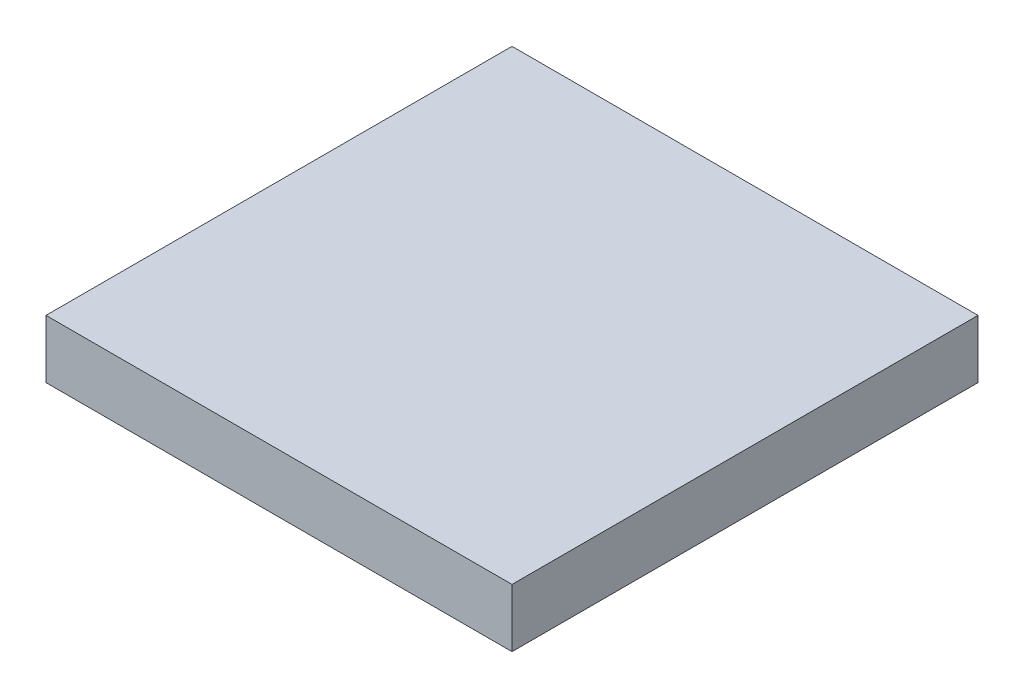
SolidWorks part; units mm, degrees
ref_plane "Plan de face" through (0, 0, 0) normal (0, 0, 1) x (1, 0, 0)
ref_plane "Plan de dessus" through (0, 0, 0) normal (0, 1, 0) x (1, 0, 0)
ref_plane "Plan de droite" through (0, 0, 0) normal (1, 0, 0) x (0, 0, -1)
sketch "Esquisse1" plane through (0, 0, 0) normal (0, 1, 0) x (1, 0, 0)
  line L1 (-120, -120) -> (120, -120)
  line L2 (-120, -120) -> (-120, 120)
  line L3 (-120, 120) -> (120, 120)
  line L4 (120, -120) -> (120, 120)
  line L5 (-120, -120) -> (120, 120) construction
  line L6 (-120, 120) -> (120, -120) construction
  point P0 (0, 0)
extrude "Boss.-Extru.1" add sketch "Esquisse1" along normal blind 30
